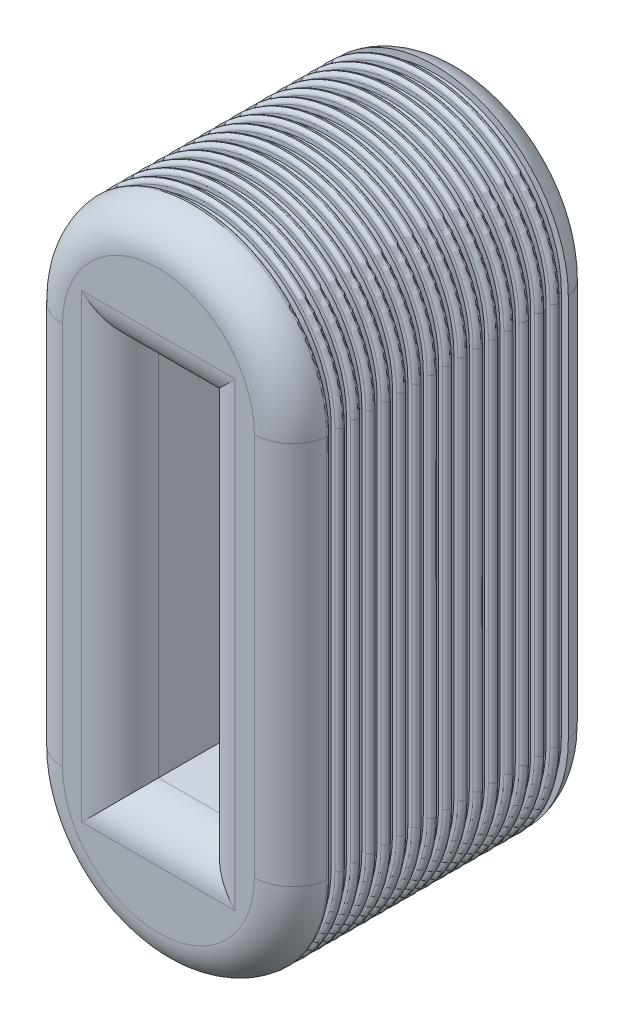
SolidWorks part; units mm, degrees
ref_plane "Front Plane" through (0, 0, 0) normal (0, 0, 1) x (1, 0, 0)
ref_plane "Top Plane" through (0, 0, 0) normal (0, 1, 0) x (1, 0, 0)
ref_plane "Right Plane" through (0, 0, 0) normal (1, 0, 0) x (0, 0, -1)
sketch "Sketch1" plane through (0, 0, 0) normal (0, 0, 1) x (1, 0, 0)
  line L0 (0, 2.5) -> (0, -2.5) construction
  line L1 (-0.5, 2.5) -> (0.5, 2.5)
  line L2 (-0.5, 2.5) -> (-0.5, -2.5)
  line L3 (-0.5, -2.5) -> (0.5, -2.5)
  line L4 (0.5, 2.5) -> (0.5, -2.5)
  line L5 (-0.5, 2.5) -> (0.5, -2.5) construction
  line L6 (-0.5, -2.5) -> (0.5, 2.5) construction
  line L7 (1.75, 2.5) -> (1.75, -2.5)
  line L8 (-1.75, 2.5) -> (-1.75, -2.5)
  arc A0 (1.75, 2.5) -> (-1.75, 2.5) centre (0, 2.5) ccw
  arc A1 (-1.75, -2.5) -> (1.75, -2.5) centre (0, -2.5) ccw
  point P0 (0, 0)
  point P8 (0, 0)
  point P13 (0, 2.5)
  dimension "D1" = 1
  dimension "D2" = 5
  dimension "D3" = 3.5
extrude "Winding profile" add sketch "Sketch1" along normal blind 4
fillet "Fillet1" radius 0.5 16 edges at (1.75, 0, 0) (0, -4.25, 0) (-1.75, 0, 0) (1.75, 0, 4) (0, -4.25, 4) (-1.75, 0, 4) (0, 4.25, 0) (0, 4.25, 4) (-0.5, 0, 4) (0, -2.5, 4) (0.5, 0, 4) (0, 2.5, 4) (0, -2.5, 0) (-0.5, 0, 0) (0, 2.5, 0) (0.5, 0, 0)
ref_plane "Plane1" through (0, 0, 3.5) normal (0, 0, -1) x (-1, 0, 0)
sketch "Sketch2" plane through (0, 0, 3.5) normal (0, 0, -1) x (-1, 0, 0)
  line L0 (1.75, -2.5) -> (1.75, 2.5) construction
  line L1 (1.75, -2.5) -> (1.75, 2.5)
  line L2 (-1.75, 2.5) -> (-1.75, -2.5) construction
  line L3 (-1.75, 2.5) -> (-1.75, -2.5)
  line L4 (-1.65, 2.5) -> (-1.65, -2.5)
  line L5 (1.65, -2.5) -> (1.65, 2.5)
  arc A0 (1.75, 2.5) -> (-1.75, 2.5) centre (0, 2.5) ccw construction
  arc A1 (1.75, 2.5) -> (-1.75, 2.5) centre (0, 2.5) ccw
  arc A2 (-1.75, -2.5) -> (1.75, -2.5) centre (0, -2.5) ccw construction
  arc A3 (-1.75, -2.5) -> (1.75, -2.5) centre (0, -2.5) ccw
  arc A4 (1.65, 2.5) -> (-1.65, 2.5) centre (0, 2.5) ccw
  arc A5 (-1.65, -2.5) -> (1.65, -2.5) centre (0, -2.5) ccw
  dimension "D1" = 0.1
extrude "Cut-Extrude1" cut sketch "Sketch2" along normal blind 0.1
pattern_linear "LPattern1" count 16 spacing 0.2 along (0, 0, -1) of "Cut-Extrude1"
fillet "Fillet3" radius 0.05 128 edges at (-1.65, 0, 0.5) (0, -4.15, 0.5) (1.65, 0, 0.5) (1.75, 0, 0.5) (0, -4.25, 0.5) (-1.75, 0, 0.5) (-1.75, 0, 0.6) (0, -4.25, 0.6) (1.75, 0, 0.6) (-1.75, 0, 0.7) (0, -4.25, 0.7) (1.75, 0, 0.7) (-1.75, 0, 0.8) (0, -4.25, 0.8) (1.75, 0, 0.8) (-1.75, 0, 0.9) (0, -4.25, 0.9) (1.75, 0, 0.9) (-1.75, 0, 1) (0, -4.25, 1) (1.75, 0, 1) (-1.75, 0, 1.1) (0, -4.25, 1.1) (1.75, 0, 1.1) (-1.75, 0, 1.2) (0, -4.25, 1.2) (1.75, 0, 1.2) (-1.75, 0, 1.3) (0, -4.25, 1.3) (1.75, 0, 1.3) (-1.75, 0, 1.4) (0, -4.25, 1.4) (1.75, 0, 1.4) (-1.75, 0, 1.5) (0, -4.25, 1.5) (1.75, 0, 1.5) (-1.75, 0, 1.6) (0, -4.25, 1.6) (1.75, 0, 1.6) (-1.75, 0, 1.7) (0, -4.25, 1.7) (1.75, 0, 1.7) (-1.75, 0, 1.8) (0, -4.25, 1.8) (1.75, 0, 1.8) (-1.75, 0, 1.9) (0, -4.25, 1.9) (1.75, 0, 1.9) (-1.75, 0, 2) (0, -4.25, 2) (1.75, 0, 2) (-1.75, 0, 2.1) (0, -4.25, 2.1) (1.75, 0, 2.1) (-1.75, 0, 2.2) (0, -4.25, 2.2) (1.75, 0, 2.2) (-1.75, 0, 2.3) (0, -4.25, 2.3) (1.75, 0, 2.3) (-1.75, 0, 2.4) (0, -4.25, 2.4) (1.75, 0, 2.4) (-1.75, 0, 2.5) (0, -4.25, 2.5) (1.75, 0, 2.5) (-1.75, 0, 2.6) (0, -4.25, 2.6) (1.75, 0, 2.6) (-1.75, 0, 2.7) (0, -4.25, 2.7) (1.75, 0, 2.7) (-1.75, 0, 2.8) (0, -4.25, 2.8) (1.75, 0, 2.8) (-1.75, 0, 2.9) (0, -4.25, 2.9) (1.75, 0, 2.9) (-1.75, 0, 3) (0, -4.25, 3) (1.75, 0, 3) (-1.75, 0, 3.1) (0, -4.25, 3.1) (1.75, 0, 3.1) (-1.75, 0, 3.2) (0, -4.25, 3.2) (1.75, 0, 3.2) (-1.75, 0, 3.3) (0, -4.25, 3.3) (1.75, 0, 3.3) (-1.75, 0, 3.4) (0, -4.25, 3.4) (1.75, 0, 3.4) (-1.75, 0, 3.5) (0, -4.25, 3.5) (1.75, 0, 3.5) (0, 4.15, 0.5) (0, 4.25, 0.5) (0, 4.25, 0.6) (0, 4.25, 0.7) (0, 4.25, 0.8) (0, 4.25, 0.9) (0, 4.25, 1) (0, 4.25, 1.1) (0, 4.25, 1.2) (0, 4.25, 1.3) (0, 4.25, 1.4) (0, 4.25, 1.5) (0, 4.25, 1.6) (0, 4.25, 1.7) (0, 4.25, 1.8) (0, 4.25, 1.9) (0, 4.25, 2) (0, 4.25, 2.1) (0, 4.25, 2.2) (0, 4.25, 2.3) (0, 4.25, 2.4) (0, 4.25, 2.5) (0, 4.25, 2.6) (0, 4.25, 2.7) (0, 4.25, 2.8) (0, 4.25, 2.9) (0, 4.25, 3) (0, 4.25, 3.1) (0, 4.25, 3.2) (0, 4.25, 3.3) (0, 4.25, 3.4) (0, 4.25, 3.5)
